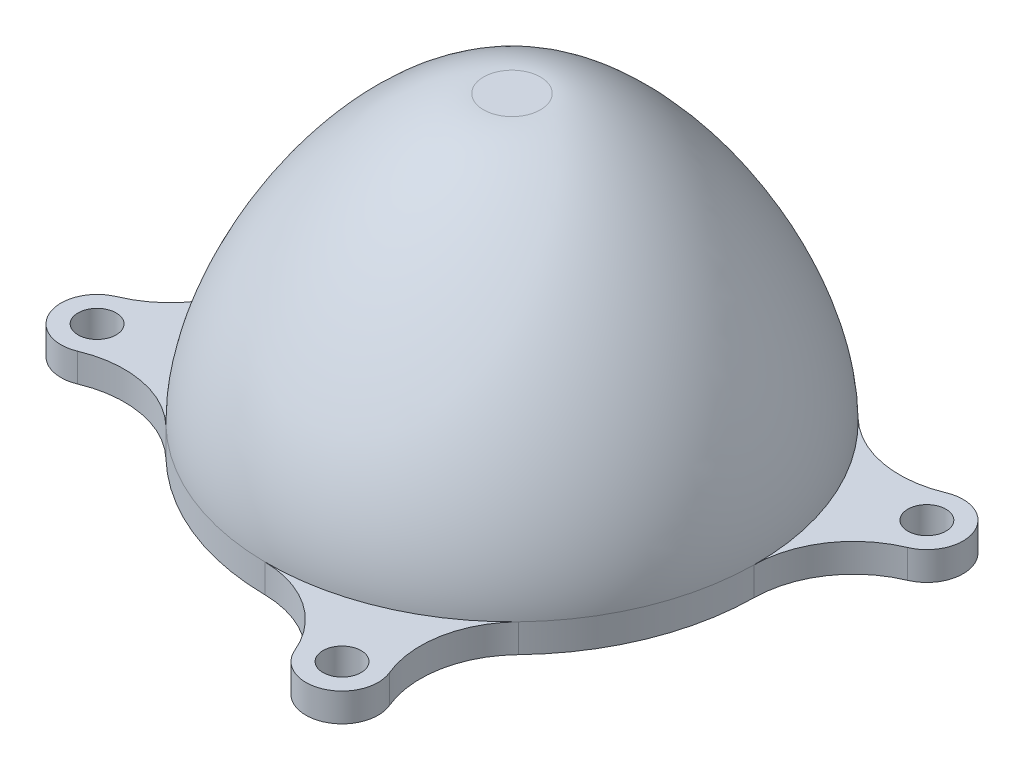
SolidWorks part; units mm, degrees
ref_plane "Front Plane" through (0, 0, 0) normal (0, 0, 1) x (1, 0, 0)
ref_plane "Top Plane" through (0, 0, 0) normal (0, 1, 0) x (1, 0, 0)
ref_plane "Right Plane" through (0, 0, 0) normal (1, 0, 0) x (0, 0, -1)
sketch "Sketch1" plane through (0, 0, 0) normal (0, 0, 1) x (1, 0, 0)
  line L1 (0, 40) -> (0, 0) construction
  line L5 (43, 0) -> (33, 0) construction
  line L6 (0, 40) -> (33, 40) construction
  line L7 (0, 0) -> (33, 0) construction
  line L13 (0, 50) -> (0, 40)
  line L14 (33, 0) -> (33, 40) construction
  line L19 (0, 50) -> (43, 50) construction
  line L20 (43, 50) -> (43, 0) construction
  line L21 (0, 50) -> (5, 50)
  line L22 (43, 0) -> (43, -5)
  line L23 (43, -5) -> (41, -5)
  line L25 (41, -5) -> (41, 0)
  line L27 (41, -5) -> (39, -5) construction
  line L28 (39, -5) -> (39, 0) construction
  line L29 (33, 0) -> (35, 0) construction
  line L30 (38, 0) -> (39, 0)
  line L31 (39, 0) -> (41, 0)
  line L32 (43, -2.5) -> (35, -2.5) construction
  line L33 (33, 0) -> (33, -2.5)
  line L34 (33, -2.5) -> (35, -2.5)
  line L36 (36.52, -2.5) -> (38, -2.5)
  line L37 (38, -2.5) -> (38, 0)
  arc A0 (35, -2.5) -> (36.52, -2.5) centre (35.76, -2.5) cw
  conic Q0 (0, 40) -> (33, 0) control (33, 40) rho 0.3
  conic Q1 (5, 50) -> (43, 0) control (43, 50) rho 0.3
  dimension "D2" = 0.76
  dimension "Foam Thickness" = 10
  dimension "Egg Height/2" = 40
  dimension "egg max radius" = 33
  dimension "base radius" = 5
  dimension "outer thread width" = 2
  dimension "thread length" = 5
  dimension "inner thread width" = 2
  dimension "o ring inner radius" = 35
  dimension "thread distance" = 1
revolve "Revolve1" add sketch "Sketch1" angle 360 about L1
thread "Thread2" pitch 1 method extrude trim with end face yes profile "Thread Profile3" start angle 0, offset 0, length 0, pitch 1, diameter 82
ref_plane "Plane3" through (-41, 0, 0) normal (0, 0, 1) x (-1, 0, 0)
sketch "Thread Profile3" plane through (-41, 0, 0) normal (0, 0, 1) x (-1, 0, 0)
  line L0 (0, 0) -> (0, 1) construction
  line L11 (0, 0) -> (0, 0.875)
  line L12 (0, 0.875) -> (-0.5413, 0.5625)
  line L13 (-0.5413, 0.5625) -> (-0.5413, 0.3125)
  line L15 (-0.5413, 0.3125) -> (0, 0)
  line L17 (-0.5413, 0.4375) -> (0, 0.4375) construction
  point P2 (0, 0)
  dimension "Pitch" = 1
  dimension "Profile_Angle" = 60
  dimension "Profile_Land" = 0.25
  dimension "Profile_Height" = 0.5413
sketch "Sketch5" plane through (0, 0, 0) normal (0, 1, 0) x (1, 0, 0)
  line L0 (15.6602, -53.8291) -> (27.3744, -48.923) construction
  line L1 (21.5173, -51.376) -> (16.6112, -39.6619) construction
  circle A0 centre (21.5173, -51.376) radius 3.35
  circle A1 centre (21.5173, -51.376) radius 6.35 construction
  arc A2 (27.3744, -48.923) -> (30.9503, -29.8509) centre (43.655, -42.1043) cw
  circle A3 centre (0, 0) radius 43 construction
  arc A4 (27.3744, -48.923) -> (15.6602, -53.8291) centre (21.5173, -51.376) cw
  arc A5 (15.6602, -53.8291) -> (-0.4399, -42.9978) centre (-0.6204, -60.6477) ccw
  arc A6 (-53.8291, -15.6602) -> (-42.9978, 0.4399) centre (-60.6477, 0.6204) ccw
  arc A7 (-48.923, -27.3744) -> (-53.8291, -15.6602) centre (-51.376, -21.5173) cw
  arc A8 (-48.923, -27.3744) -> (-29.8509, -30.9503) centre (-42.1043, -43.655) cw
  arc A9 (-15.6602, 53.8291) -> (0.4399, 42.9978) centre (0.6204, 60.6477) ccw
  arc A10 (-27.3744, 48.923) -> (-15.6602, 53.8291) centre (-21.5173, 51.376) cw
  arc A11 (-27.3744, 48.923) -> (-30.9503, 29.8509) centre (-43.655, 42.1043) cw
  arc A12 (53.8291, 15.6602) -> (42.9978, -0.4399) centre (60.6477, -0.6204) ccw
  arc A13 (48.923, 27.3744) -> (53.8291, 15.6602) centre (51.376, 21.5173) cw
  arc A14 (48.923, 27.3744) -> (29.8509, 30.9503) centre (42.1043, 43.655) cw
  arc A15 (-0.4399, -42.9978) -> (30.9503, -29.8509) centre (0, 0) ccw
  arc A16 (-42.9978, 0.4399) -> (-29.8509, -30.9503) centre (0, 0) ccw
  arc A17 (0.4399, 42.9978) -> (-30.9503, 29.8509) centre (0, 0) ccw
  arc A18 (42.9978, -0.4399) -> (29.8509, 30.9503) centre (0, 0) ccw
  circle A19 centre (-51.376, -21.5173) radius 3.35
  circle A20 centre (-21.5173, 51.376) radius 3.35
  circle A21 centre (51.376, 21.5173) radius 3.35
  circle A22 centre (21.5173, -51.376) radius 3 construction
  point P37 (0, 0)
  dimension "D1" = 6.7
  dimension "D3" = 3
  dimension "D2" = 4
extrude "Boss-Extrude1" add sketch "Sketch5" against normal up to surface (5 mm away)
